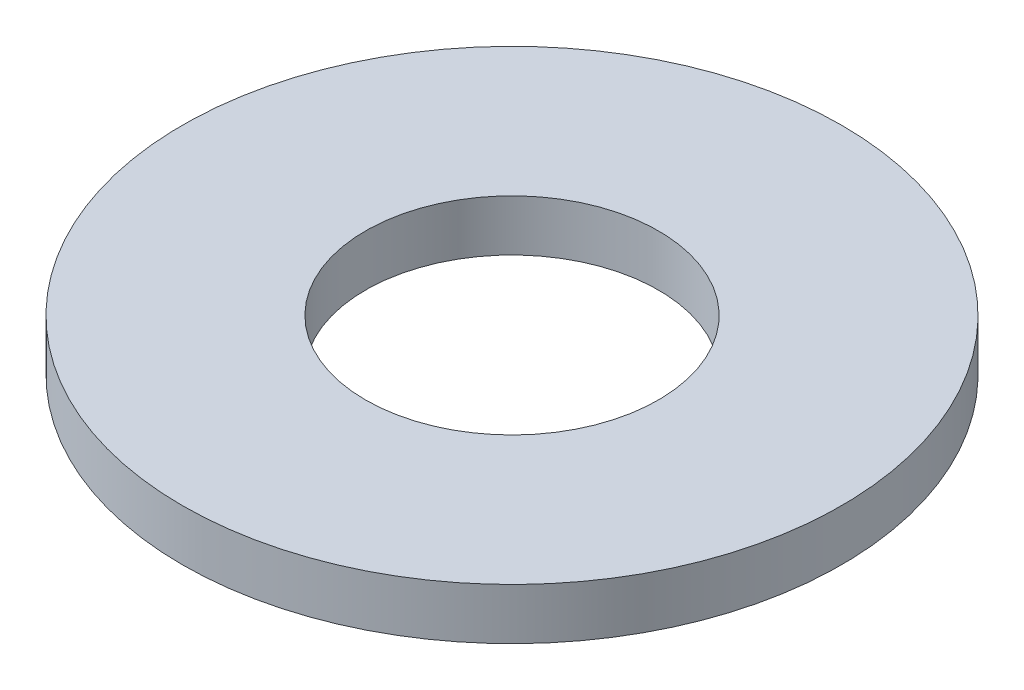
SolidWorks part; units mm, degrees
ref_plane "Front Plane" through (0, 0, 0) normal (0, 0, 1) x (1, 0, 0)
ref_plane "Top Plane" through (0, 0, 0) normal (0, 1, 0) x (1, 0, 0)
ref_plane "Right Plane" through (0, 0, 0) normal (1, 0, 0) x (0, 0, -1)
sketch "Sketch1" plane through (0, 0, 0) normal (0, 1, 0) x (1, 0, 0)
  circle A0 centre (0, 0) radius 90
  dimension "FLANGE_OD" = 180
extrude "Boss-Extrude1" add sketch "Sketch1" along normal blind 14
sketch "Sketch2" plane through (0, 0, 0) normal (0, 1, 0) x (1, 0, 0)
  circle A0 centre (0, 0) radius 40
  dimension "BORE_D" = 80
extrude "Cut-Extrude1" cut sketch "Sketch2" along normal through all
sketch "Sketch3" plane through (0, 14, 0) normal (0, 1, 0) x (1, 0, 0)
  circle A0 centre (0, 0) radius 34.5542 construction
  circle A1 centre (-34.5542, 0) radius 2.2982
  dimension "BOLT_D" = 4.5964
  dimension "BOLT_PCD" = 69.1084
extrude "Cut-Extrude2" cut sketch "Sketch3" against normal blind 9.6225 rebuild error yes
pattern_circular "CirPattern1" count 6 over 360 rebuild error yes
